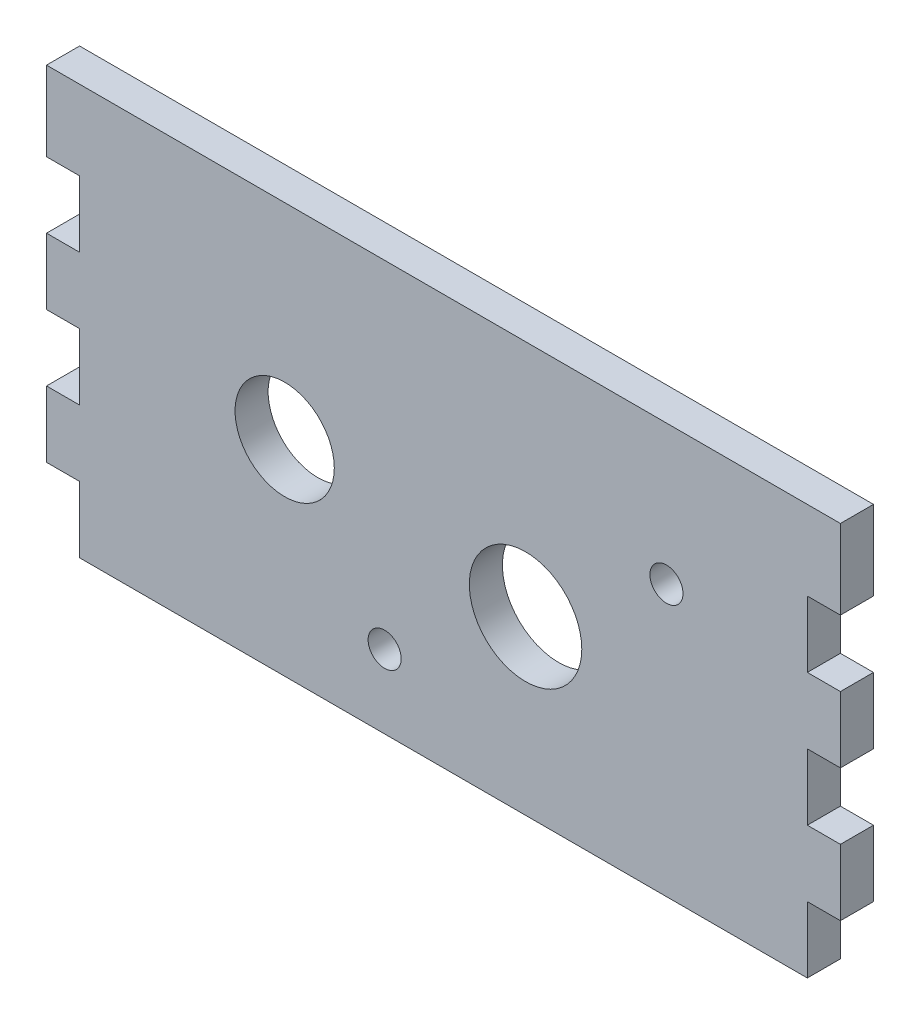
SolidWorks part; units mm, degrees
ref_plane "정면" through (0, 0, 0) normal (0, 0, 1) x (1, 0, 0)
ref_plane "윗면" through (0, 0, 0) normal (0, 1, 0) x (1, 0, 0)
ref_plane "우측면" through (0, 0, 0) normal (1, 0, 0) x (0, 0, -1)
sketch "스케치2" plane through (0, 0, 0) normal (0, 0, 1) x (1, 0, 0)
  line L0 (-6.0717, -5) -> (65.5766, -5) construction
  line L1 (-60, -31) -> (60, -31)
  line L2 (-60, -31) -> (-60, 31)
  line L3 (-60, 31) -> (60, 31)
  line L4 (60, -31) -> (60, 31)
  line L5 (-60, -31) -> (60, 31) construction
  line L6 (-60, 31) -> (60, -31) construction
  line L7 (-15.8273, -24.7708) -> (37.7136, 12.7189) construction
  circle A0 centre (12.4083, -5) radius 8.5
  circle A1 centre (-24, 0) radius 7.5
  circle A2 centre (33.7062, 9.913) radius 2.5
  circle A3 centre (-8.8897, -19.913) radius 2.5
  point P0 (0, 0)
  dimension "D5" = 17
  dimension "D8" = 15
  dimension "D9" = 35
  dimension "D10" = 5
  dimension "D1" = 62
  dimension "D2" = 120
  dimension "D3" = 36.75
  dimension "D4" = 36
  dimension "D6" = 31
  dimension "D7" = 36
  dimension "D11" = 26
  dimension "D12" = 26
extrude "보스-돌출1" add sketch "스케치2" along normal blind 5 contours L1 L4 L3 L2 A1 A0 region at (0.134, 0.1903, 0)
sketch "스케치3" plane through (0, 0, 5) normal (0, 0, 1) x (1, 0, 0)
  line L0 (-60, -31) -> (-60, 31) construction
  line L1 (-60, -21) -> (-55, -21)
  line L2 (-60, -21) -> (-60, -31)
  line L3 (-60, -31) -> (-55, -31)
  line L4 (-55, -21) -> (-55, -31)
  line L5 (-60, -31) -> (60, -31) construction
  dimension "D1" = 5
  dimension "D2" = 10
extrude "컷-돌출1" cut sketch "스케치3" against normal up to next
pattern_linear "선형 패턴1" count 3 spacing 20 along (0, 1, 0) of "컷-돌출1"
mirror "대칭 복사1" about plane through (0, 0, 0) normal (1, 0, 0) of "선형 패턴1"
